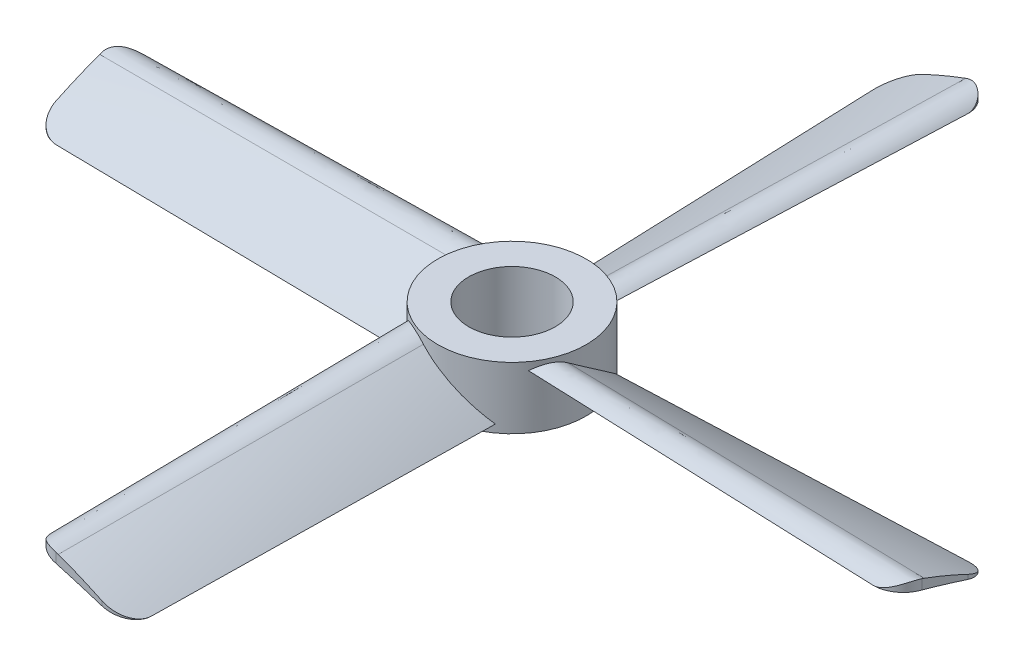
SolidWorks part; units mm, degrees
ref_plane "前视基准面" through (0, 0, 0) normal (0, 0, 1) x (1, 0, 0)
ref_plane "上视基准面" through (0, 0, 0) normal (0, 1, 0) x (1, 0, 0)
ref_plane "右视基准面" through (0, 0, 0) normal (1, 0, 0) x (0, 0, -1)
sketch "草图1" plane through (0, 0, 0) normal (0, 1, 0) x (1, 0, 0)
  circle A0 centre (0, 0) radius 6
  dimension "D1" = 12
extrude "凸台-拉伸1" add sketch "草图1" along normal blind 5
ref_plane "基准面1" through (0, 0, 35) normal (0, 0, 1) x (1, 0, 0)
sketch "草图2" plane through (0, 0, 35) normal (0, 0, 1) x (1, 0, 0)
  line L0 (0, 0) -> (0, 2.5) construction
  line L1 (0, 2.5) -> (3.8637, 1.4647) construction
  line L2 (0, 2.5) -> (-3.8637, 3.5353) construction
  line L3 (-3.8637, 3.5353) -> (-3.6049, 4.5012) construction
  line L4 (-3.6049, 4.5012) -> (-1.673, 3.9836) construction
  line L5 (-1.673, 3.9836) -> (-1.8671, 3.2591) construction
  arc A0 (-3.8637, 3.5353) -> (-1.673, 3.9836) centre (-2.4359, 2.1348) cw
  arc A1 (-1.673, 3.9836) -> (3.8637, 1.4647) centre (-15.4205, -33.5798) cw
  arc A2 (-3.8637, 3.5353) -> (-1.8671, 3.2591) centre (-4.5038, -8.4476) cw
  arc A3 (-1.8671, 3.2591) -> (3.8637, 1.4647) centre (-28.8689, -93.0264) cw
  dimension "D9" = 2
  dimension "D10" = 40
  dimension "D13" = 12
  dimension "D14" = 100
  dimension "D1" = 2.5
  dimension "D2" = 4
  dimension "D3" = 4
  dimension "D4" = 75
  dimension "D5" = 105
  dimension "D6" = 90
  dimension "D7" = 1
  dimension "D8" = 2
  dimension "D11" = 90
  dimension "D12" = 0.75
sketch "草图3" plane through (0, 0, 0) normal (0, 0, 1) x (1, 0, 0)
  line L0 (0, 0) -> (0, 2.5) construction
  line L1 (0, 2.5) -> (-3.4641, 4.5) construction
  line L2 (0, 2.5) -> (3.4641, 0.5) construction
  line L3 (-3.4641, 4.5) -> (-2.9641, 5.366) construction
  line L4 (-2.9641, 5.366) -> (-1.2321, 4.366) construction
  line L5 (-1.2321, 4.366) -> (-1.6071, 3.7165) construction
  arc A1 (-3.4641, 4.5) -> (-1.2321, 4.366) centre (-2.4474, 2.7777) cw
  arc A2 (-1.6071, 3.7165) -> (3.4641, 0.5) centre (-52.6093, -82.2996) cw
  arc A3 (-1.2321, 4.366) -> (3.4641, 0.5) centre (-24.2332, -28.3593) cw
  arc A4 (-3.4641, 4.5) -> (-1.6071, 3.7165) centre (-7.1838, -6.909) cw
  dimension "D2" = 120
  dimension "D11" = 2
  dimension "D12" = 12
  dimension "D13" = 40
  dimension "D14" = 100
  dimension "D1" = 4
  dimension "D3" = 60
  dimension "D4" = 4
  dimension "D5" = 90
  dimension "D6" = 1
  dimension "D7" = 90
  dimension "D8" = 2
  dimension "D9" = 90
  dimension "D10" = 0.75
loft "放样1" add profiles "草图2", "草图3" connector at (-3.8637, 3.5353, 35) connector at (-3.4641, 4.5, 0)
sketch "草图5" plane through (0, 0, 0) normal (0, 1, 0) x (1, 0, 0)
  line L0 (-3.5196, -4.8593) -> (-3.8406, -32.9772)
  line L2 (-3.5196, -4.8593) -> (-4.5196, -4.8593)
  line L4 (-1.8407, -35) -> (1.8407, -35)
  line L5 (-4.5196, -4.8593) -> (-4.5196, -35.8593)
  line L7 (3.8406, -32.9772) -> (3.5196, -4.8593)
  line L8 (-4.5196, -35.8593) -> (4.5196, -35.8593)
  line L9 (4.5196, -35.8593) -> (4.5196, -4.8593)
  line L10 (4.5196, -4.8593) -> (3.5196, -4.8593)
  arc A0 (-3.5196, -4.8593) -> (3.5196, -4.8593) centre (0, 0) ccw
  arc A1 (-3.8406, -32.9772) -> (-1.8407, -35) centre (-1.8407, -33) ccw
  arc A2 (1.8407, -35) -> (3.8406, -32.9772) centre (1.8407, -33) ccw
  dimension "D1" = 6
  dimension "D2" = 4
  dimension "D3" = 4
  dimension "D4" = 1
  dimension "D5" = 1
  dimension "D6" = 31
extrude "切除-拉伸1" cut sketch "草图5" along normal through all contours A2 L4 A1 L0 L2 L5 L8 L9 L10 L7 region at (-4.003, 0, 18.9145)
pattern_circular "阵列(圆周)1" count 4 over 360 about axis through (0, 5, 0) along (0, -1, 0) of "放样1", "切除-拉伸1"
sketch "草图6" plane through (0, 5, 0) normal (0, 1, 0) x (1, 0, 0)
  circle A0 centre (0, 0) radius 3.5
  dimension "D1" = 7
extrude "切除-拉伸2" cut sketch "草图6" against normal through all
